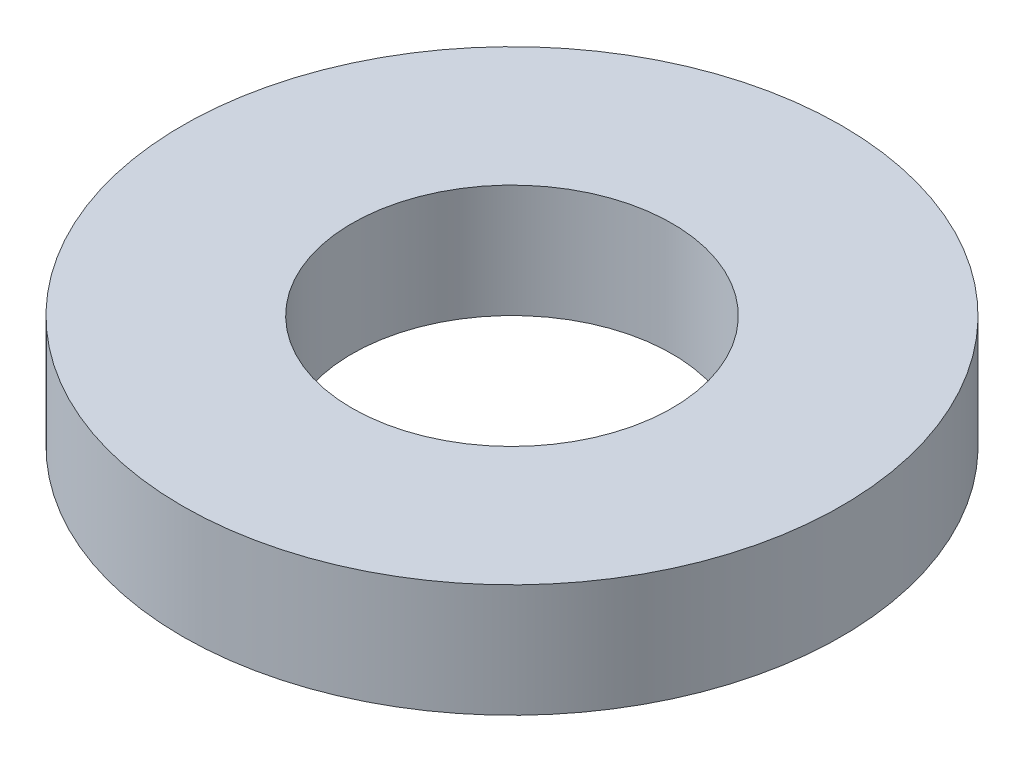
SolidWorks part; units mm, degrees
ref_plane "Front Plane" through (0, 0, 0) normal (0, 0, 1) x (1, 0, 0)
ref_plane "Top Plane" through (0, 0, 0) normal (0, 1, 0) x (1, 0, 0)
ref_plane "Right Plane" through (0, 0, 0) normal (1, 0, 0) x (0, 0, -1)
sketch "Sketch1" plane through (0, 0, 0) normal (0, 1, 0) x (1, 0, 0)
  circle A0 centre (0, 0) radius 87.5
  dimension "FLANGE_OD" = 175
extrude "Boss-Extrude1" add sketch "Sketch1" along normal blind 30
sketch "Sketch2" plane through (0, 0, 0) normal (0, 1, 0) x (1, 0, 0)
  circle A0 centre (0, 0) radius 42.5
  dimension "BORE_D" = 85
extrude "Cut-Extrude1" cut sketch "Sketch2" along normal through all
sketch "Sketch3" plane through (0, 30, 0) normal (0, 1, 0) x (1, 0, 0)
  circle A0 centre (0, 0) radius 23.8716 construction
  circle A1 centre (-23.8716, 0) radius 1.7957
  dimension "BOLT_D" = 3.5914
  dimension "BOLT_PCD" = 47.7433
extrude "Cut-Extrude2" cut sketch "Sketch3" against normal blind 22.3671 rebuild error yes
pattern_circular "CirPattern1" count 5 over 360 rebuild error yes
